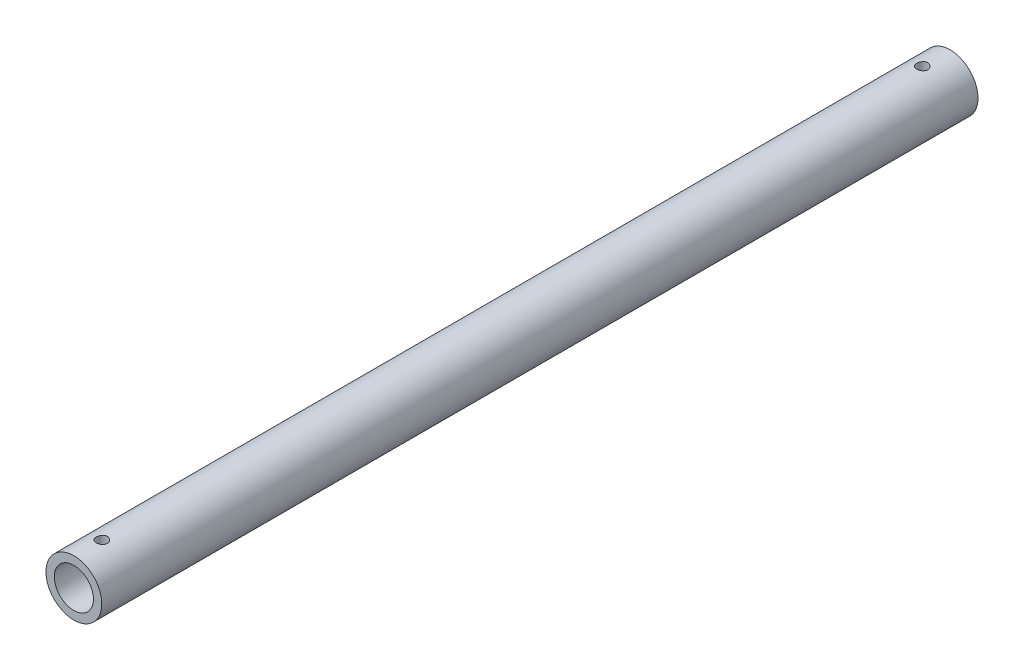
SolidWorks part; units mm, degrees
material "PLA"
ref_plane "Plan de face" through (0, 0, 0) normal (0, 0, 1) x (1, 0, 0)
ref_plane "Plan de dessus" through (0, 0, 0) normal (0, 1, 0) x (1, 0, 0)
ref_plane "Plan de droite" through (0, 0, 0) normal (1, 0, 0) x (0, 0, -1)
sketch "Esquisse1" plane through (0, 0, 0) normal (0, 0, 1) x (1, 0, 0)
  circle A0 centre (0, 0) radius 5
  circle A1 centre (0, 0) radius 3.505
  dimension "D1" = 7.01
  dimension "D2" = 10
extrude "Boss.-Extru.1" add sketch "Esquisse1" along normal blind 157
sketch "Esquisse2" plane through (0, 0, 0) normal (0, 1, 0) x (1, 0, 0)
  line L0 (-5, -157) -> (5, -157) construction
  line L1 (-5, 0) -> (-5, -157) construction
  line L2 (5, -157) -> (5, 0) construction
  line L3 (5, 0) -> (-5, 0) construction
  circle A0 centre (0, -152) radius 1
  circle A1 centre (0, -5) radius 1
  dimension "D2" = 2
  dimension "D6" = 2
  dimension "D1" = 5
  dimension "D3" = 5
  dimension "D4" = 5
  dimension "D5" = 5
extrude "Enlèv. mat.-Extru.1" cut sketch "Esquisse2" against normal blind 10 and the other way blind 10
